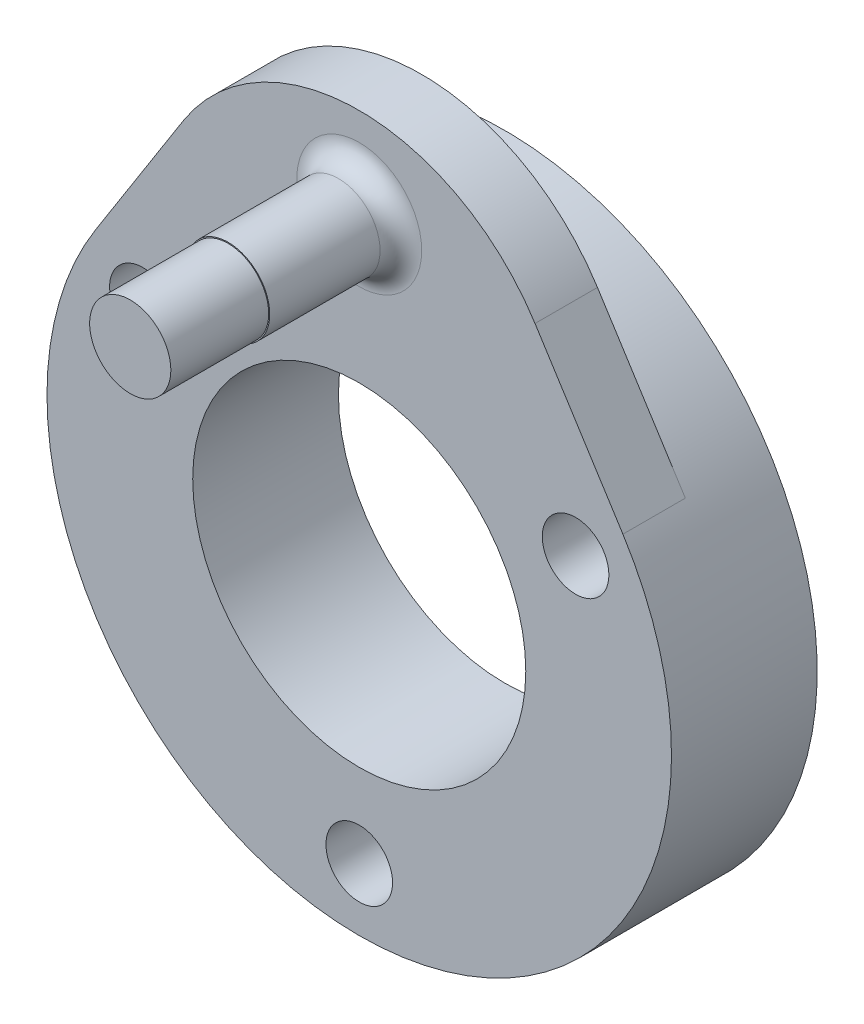
SolidWorks part; units mm, degrees
material "6061 合金"
ref_plane "前视基准面" through (0, 0, 0) normal (0, 0, 1) x (1, 0, 0)
ref_plane "上视基准面" through (0, 0, 0) normal (0, 1, 0) x (1, 0, 0)
ref_plane "右视基准面" through (0, 0, 0) normal (1, 0, 0) x (0, 0, -1)
other "Configuration Table"
sketch "草图1" plane through (0, 0, 0) normal (0, 0, 1) x (1, 0, 0)
  line L0 (0, 0) -> (0, 15) construction
  line L1 (0, 15) -> (0, 28) construction
  line L2 (0, 28) -> (12.666, 8.0357)
  line L3 (0, 28) -> (-12.666, 8.0357)
  line L4 (0, 0) -> (0, -15) construction
  line L5 (10.3923, -6) -> (0, 0) construction
  circle A0 centre (0, 0) radius 15 construction
  arc A2 (-12.666, 8.0357) -> (12.666, 8.0357) centre (0, 0) ccw
  circle A3 centre (0, 0) radius 12 construction
  circle A9 centre (0, 0) radius 8
  dimension "D1" = 30
  dimension "D5" = 24
  dimension "D9" = 16
  dimension "D2" = 15
  dimension "D4" = 13
  dimension "D7" = 60
extrude "凸台-拉伸1" add sketch "草图1" along normal blind 3
fillet "圆角1" radius 10 1 edges at (0, 28, 1.5)
sketch "草图6" plane through (0, 0, 0) normal (0, 0, -1) x (-1, 0, 0)
  line L0 (0, 0) -> (-10.3923, -6) construction
  line L2 (0, 0) -> (10.3923, -6) construction
  line L3 (0, 0) -> (0, -15) construction
  circle A4 centre (0, 0) radius 8
  arc A5 (-12.666, 8.0357) -> (12.666, 8.0357) centre (0, 0) ccw construction
  circle A6 centre (0, 0) radius 15
  circle A7 centre (0, 0) radius 8 construction
  dimension "D5" = 60
  dimension "D6" = 60
  dimension "D7" = 12
  dimension "D8" = 12
extrude "凸台-拉伸2" add sketch "草图6" along normal blind 4
sketch "草图2" plane through (0, 0, 3) normal (0, 0, 1) x (1, 0, 0)
  line L0 (0, 0) -> (0, -15) construction
  arc A0 (-12.666, 8.0357) -> (12.666, 8.0357) centre (0, 0) ccw construction
  point P6 (0, -12)
  point P7 (-10.3923, 6)
  point P10 (10.3923, 6)
  dimension "D1" = 12
  dimension "D2" = 3
hole_wizard "Ø3.0mm 暗销孔2" positions "草图2" profile "草图3" hole size "Ø3.0" standard "GB" end condition up to next
sketch "草图3" plane through (10.3923, 6, 3) normal (1, 0, 0) x (0, -1, 0)
  line L0 (0, 0) -> (0, 7)
  line L1 (0, 7) -> (1.6, 7)
  line L2 (1.6, 7) -> (1.6, 0)
  line L5 (1.6, 0) -> (0, 0)
  line L11 (0, -6.35) -> (0, 107.95) construction
  dimension "通孔孔直径" = 3.2
  dimension "通孔孔深度" = 7
sketch "草图9" plane through (0, 0, -4) normal (0, 0, -1) x (-1, 0, 0)
  line L0 (0, 0) -> (10.3923, -6) construction
  line L1 (0, 0) -> (0, -12) construction
  line L2 (0, 0) -> (-10.3923, -6) construction
  circle A0 centre (0, 0) radius 12 construction
  point P7 (10.3923, -6)
  point P8 (-10.3923, -6)
  point P9 (0, 12)
  dimension "D1" = 24
  dimension "D2" = 60
  dimension "D3" = 60
hole_wizard "Ø3.0mm 暗销孔1" positions "草图9" profile "草图10" hole size "Ø3.0" standard "GB"
sketch "草图10" plane through (0, 12, -4) normal (1, 0, 0) x (0, 1, 0)
  line L0 (0, 0) -> (0, 3.9013)
  line L1 (0, 3.9013) -> (1.5, 3)
  line L2 (1.5, 3) -> (1.5, 0)
  line L5 (1.5, 0) -> (0, 0)
  line L10 (0, 3.9013) -> (-1.5, 3) construction
  line L11 (0, -6.35) -> (0, 107.95) construction
  dimension "孔直径" = 3
  dimension "孔深度" = 3
  dimension "导头角度" = 118
sketch "草图11" plane through (0, 0, 3) normal (0, 0, 1) x (1, 0, 0)
  circle A0 centre (0, 15) radius 2
  dimension "D1" = 15
  dimension "D2" = 4
extrude "凸台-拉伸3" add sketch "草图11" along normal blind 6.3
fillet "圆角2" radius 1 1 edges at (2, 15, 3)
sketch "草图12" plane through (0, 0, 9.3) normal (0, 0, 1) x (1, 0, 0)
  circle A0 centre (0, 15) radius 1.95
  dimension "D1" = 3.9
extrude "凸台-拉伸4" add sketch "草图12" along normal blind 4.7
sketch "草图13" plane through (0, 0, 3) normal (0, 0, 1) x (1, 0, 0)
  line L0 (0, 0) -> (0, 15)
